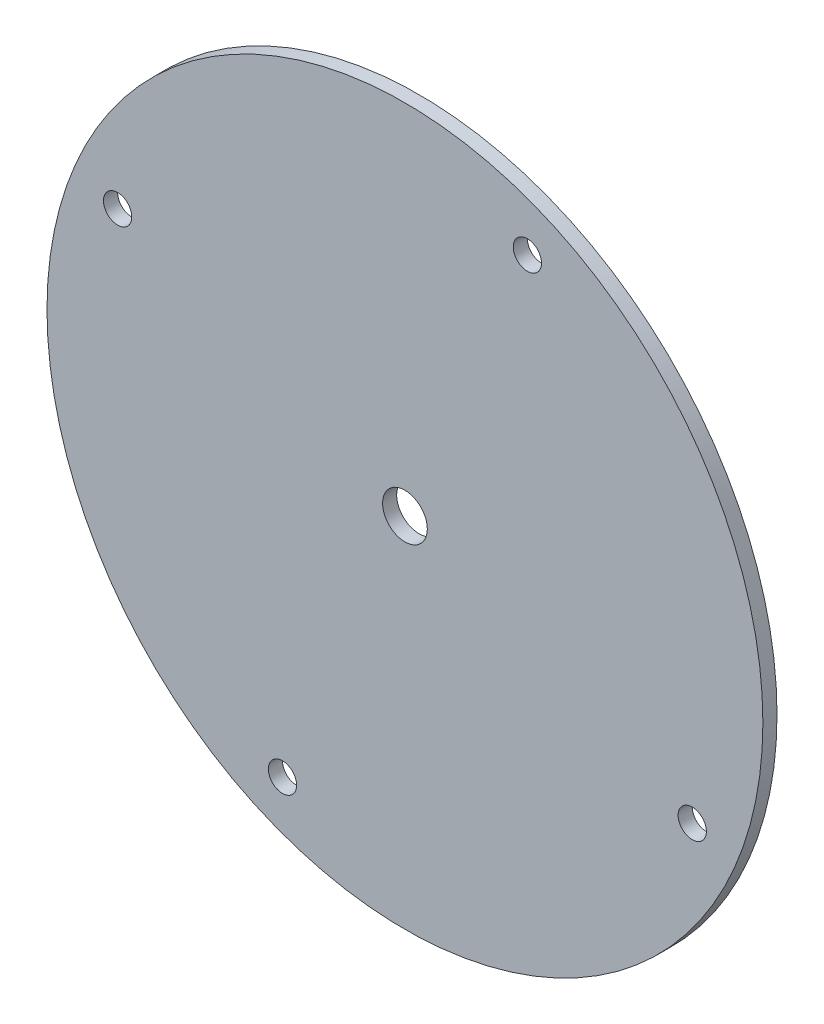
SolidWorks part; units mm, degrees
material "1060 Alloy"
ref_plane "Front Plane" through (0, 0, 0) normal (0, 0, 1) x (1, 0, 0)
ref_plane "Top Plane" through (0, 0, 0) normal (0, 1, 0) x (1, 0, 0)
ref_plane "Right Plane" through (0, 0, 0) normal (1, 0, 0) x (0, 0, -1)
sketch "Sketch1" plane through (0, 0, 0) normal (0, 0, 1) x (1, 0, 0)
  line L5 (50, -50) -> (-50, 50) construction
  line L6 (50, 50) -> (-50, -50) construction
  line L31 (20.5, 61) -> (23.25, 56.2369)
  line L32 (23.25, 56.2369) -> (28.75, 56.2369)
  line L33 (28.75, 56.2369) -> (31.5, 61)
  line L36 (-38.9, 50) -> (38.9, 50) construction
  line L50 (0, -76) -> (0, 122.6166) construction
  line L51 (-76, 0) -> (103.3867, 0) construction
  line L52 (31.5, 61) -> (28.75, 65.7631)
  line L53 (28.75, 65.7631) -> (23.25, 65.7631)
  line L54 (23.25, 65.7631) -> (20.5, 61)
  line L55 (-61, 20.5) -> (-56.2369, 23.25)
  line L56 (-56.2369, 23.25) -> (-56.2369, 28.75)
  line L57 (-56.2369, 28.75) -> (-61, 31.5)
  line L58 (-61, 31.5) -> (-65.7631, 28.75)
  line L59 (-65.7631, 28.75) -> (-65.7631, 23.25)
  line L60 (-65.7631, 23.25) -> (-61, 20.5)
  line L61 (61, -20.5) -> (56.2369, -23.25)
  line L62 (56.2369, -23.25) -> (56.2369, -28.75)
  line L96 (56.2369, -28.75) -> (61, -31.5)
  line L97 (61, -31.5) -> (65.7631, -28.75)
  line L98 (65.7631, -28.75) -> (65.7631, -23.25)
  line L99 (65.7631, -23.25) -> (61, -20.5)
  line L100 (-20.5, -61) -> (-23.25, -56.2369)
  line L101 (-23.25, -56.2369) -> (-28.75, -56.2369)
  line L102 (-28.75, -56.2369) -> (-31.5, -61)
  line L103 (-31.5, -61) -> (-28.75, -65.7631)
  line L104 (-28.75, -65.7631) -> (-23.25, -65.7631)
  line L105 (-23.25, -65.7631) -> (-20.5, -61)
  arc A0 (0, 76) -> (-72.0169, -24.281) centre (0, 0) ccw
  circle A1 centre (26, 61) radius 3
  arc A2 (76, 0) -> (0, 76) centre (0, 0) ccw
  arc A3 (-72.0169, -24.281) -> (0, -76) centre (0, 0) ccw
  arc A4 (0, -76) -> (76, 0) centre (0, 0) ccw
  circle A5 centre (61, -26) radius 3
  circle A6 centre (-26, -61) radius 3
  circle A7 centre (-61, 26) radius 3
  circle A8 centre (26, 61) radius 5.5 construction
  circle A9 centre (-61, 26) radius 5.5 construction
  circle A10 centre (61, -26) radius 5.5 construction
  circle A11 centre (-26, -61) radius 5.5 construction
  dimension "D1" = 152
  dimension "D9" = 26
  dimension "D15" = 11
  dimension "D16" = 11
  dimension "D17" = 11
  dimension "D3" = 26
  dimension "D10" = 26
  dimension "D11" = 26
extrude "Boss-Extrude3" add sketch "Sketch1" along normal blind 3 contours A4 A2 A0 A3 L105 L104 L103 L102 L101 L100 L99 L98 L97 L96 L62 L61 L60 L59 L58 L57 L56 L55 L54 L53 L52 L33 L32 L31 | L59 L60 L55 L56 L57 L58 A7 | L53 L54 L31 L32 L33 L52 A1 | L98 L99 L61 L62 L96 L97 A5 | L104 L105 L100 L101 L102 L103 A6 region at (22.001, 63.3088, 0) region at (-63.3088, 22.001, 0) region at (63.3088, -22.001, 0) region at (-22.001, -63.3088, 0) region at (0, 0, 0)
sketch "Sketch2" plane through (0, 0, 3) normal (0, 0, 1) x (1, 0, 0)
  circle A0 centre (0, 0) radius 4.75
  dimension "D1" = 9.5
extrude "Cut-Extrude1" cut sketch "Sketch2" against normal through all
